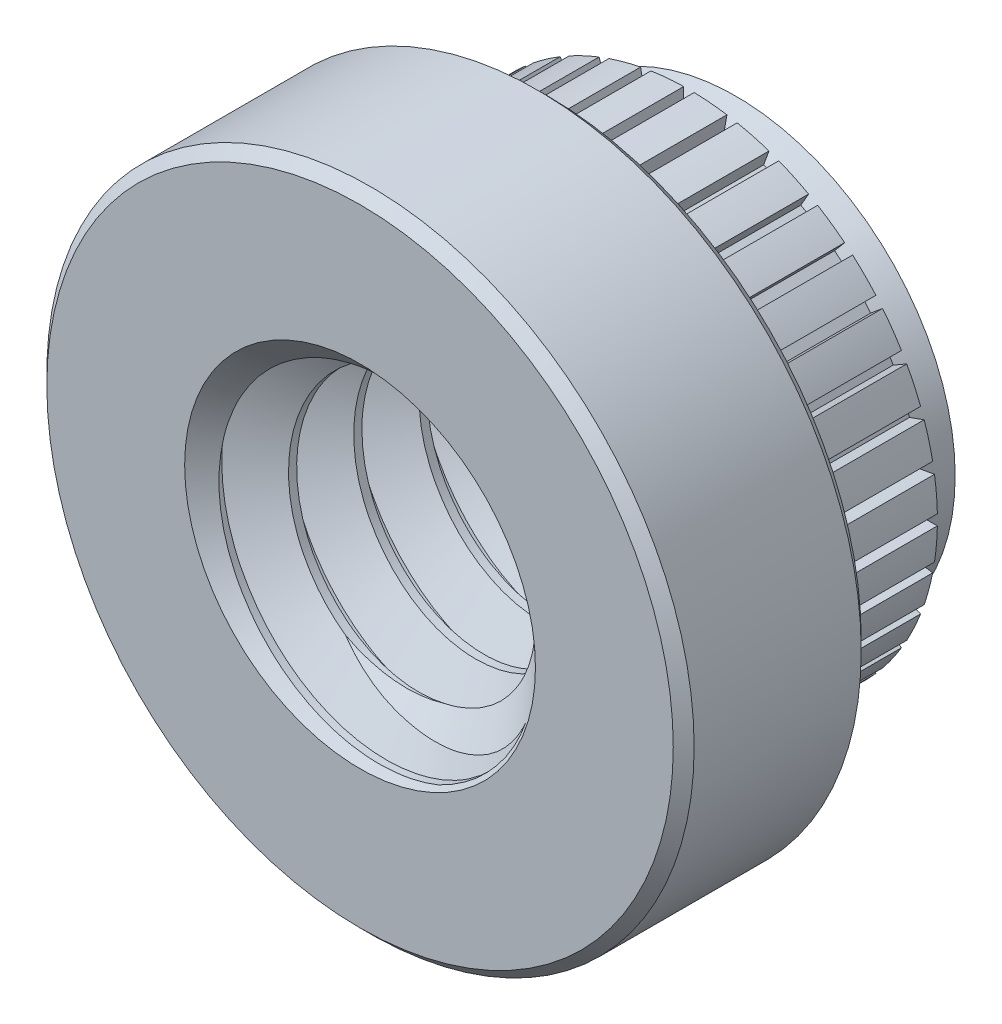
SolidWorks part; units mm, degrees
ref_plane "Front Plane" through (0, 0, 0) normal (0, 0, 1) x (1, 0, 0)
ref_plane "Top Plane" through (0, 0, 0) normal (0, 1, 0) x (1, 0, 0)
ref_plane "Right Plane" through (0, 0, 0) normal (1, 0, 0) x (0, 0, -1)
sketch "Sketch1" plane through (0, 0, 0) normal (0, 0, 1) x (1, 0, 0)
  circle A0 centre (0, 0) radius 3.937
  dimension "A" = 7.874
extrude "Extrude1" add sketch "Sketch1" against normal blind 2.286
sketch "Sketch15" plane through (0, 0, -2.286) normal (0, 0, -1) x (-1, 0, 0)
  circle A0 centre (0, 0) radius 2.7051
  dimension "hole dia" = 5.4102
sketch "Sketch2" plane through (0, 0, -2.286) normal (0, 0, -1) x (-1, 0, 0)
  circle A0 centre (0, 0) radius 3.0226
  dimension "D1" = 6.0452
extrude "Extrude2" add sketch "Sketch2" along normal blind 2.286
sketch "Sketch3" plane through (0, 0, -4.572) normal (0, 0, -1) x (-1, 0, 0)
  line L0 (0, 2.8321) -> (0, 3.937)
  circle A1 centre (0, 0) radius 3.937 construction
  circle A2 centre (0, 0) radius 2.8321
  circle A3 centre (0, 0) radius 2.8321 construction
  dimension "D1" = 0.1905
extrude "Cut-Extrude-Thin1" cut sketch "Sketch3" against normal up to surface (2.286 mm away) thin up to face at (3.937, 0, -2.286) thin type mid plane wall 0.127
pattern_circular "CirPattern1" count 36 over 360 about axis through (0, 0, 0) along (0, 0, 1) of "Cut-Extrude-Thin1"
sketch "Sketch5" plane through (0, 0, -4.572) normal (0, 0, -1) x (-1, 0, 0)
  circle A0 centre (0, 0) radius 3.937 construction
  circle A3 centre (0, 0) radius 2.667
  dimension "C" = 5.334
extrude "Cut-Extrude1" cut sketch "Sketch5" against normal blind 0.5715 draft 20 flip side to cut draft outward yes
chamfer "Chamfer2" distance 0.127 angle 45 2 edges at (3.937, 0, 0) (3.937, 0, -2.286)
sketch "Sketch7" plane through (0, 0, 0) normal (0, 0, 1) x (1, 0, 0)
  circle A0 centre (0, 0) radius 2.0828
  dimension "Thread Od" = 4.1656
extrude "Cut-Extrude3" cut sketch "Sketch7" against normal through all
sketch "Sketch8" plane through (0, 0, -4.572) normal (0, 0, -1) x (-1, 0, 0)
  circle A0 centre (0, 0) radius 2.0828 construction
  circle A1 centre (0, 0) radius 2.0828
curve "Helix/Spiral1" pitch 0.7937 height 7.747 turns 9.76 parameters "pitch"=0.7937
sketch "Sketch9" plane through (0, 0, 0) normal (1, 0, 0) x (0, 0, -1)
  line L0 (5.2665, 2.0828) -> (4.9689, 1.5672)
  line L1 (4.9689, 1.5672) -> (4.8697, 1.5672)
  line L2 (4.8697, 1.5672) -> (4.572, 2.0828)
  line L3 (5.2665, 2.0828) -> (4.572, 2.0828)
  line L4 (4.9193, 2.0828) -> (4.9193, 1.5672) construction
  line L5 (5.1177, 1.825) -> (4.7208, 1.825) construction
  line L6 (4.572, -2.0828) -> (4.572, 2.0828) construction
  dimension "D1" = 60
  dimension "D2" = 0.0992
  dimension "D3" = 0.3969
sweep "Sweep1" add profiles "Sketch9" path "Helix/Spiral1"
sketch "Sketch10" plane through (0, 0, 0) normal (0, 0, 1) x (1, 0, 0)
  circle A0 centre (0, 0) radius 3.937 construction
  circle A1 centre (0, 0) radius 3.937
extrude "Cut-Extrude4" cut sketch "Sketch10" along normal through all
sketch "Sketch11" plane through (0, 0, -4.572) normal (0, 0, -1) x (-1, 0, 0)
  circle A1 centre (0, 0) radius 2.667 construction
  circle A2 centre (0, 0) radius 2.667
extrude "Cut-Extrude5" cut sketch "Sketch11" along normal through all
sketch "Sketch13" plane through (0, 0, 0) normal (0, 0, 1) x (1, 0, 0)
  circle A2 centre (0, 0) radius 2.1336
  circle A3 centre (0, 0) radius 2.1336
  dimension "D1" = 0.0508
extrude "Cut-Extrude6" cut sketch "Sketch13" against normal through all draft 45
sketch "Sketch14" plane through (0, 0, -4.572) normal (0, 0, -1) x (-1, 0, 0)
  circle A2 centre (0, 0) radius 2.1336
  circle A3 centre (0, 0) radius 2.1336
  dimension "D1" = 0.0508
extrude "Cut-Extrude7" cut sketch "Sketch14" against normal through all draft 45
equation "\"D3@Helix/Spiral1\" = \"B@Extrude1\"+\"panel min.@Extrude2\"+.125"
equation "\"D2@Sketch9\" = \"pitch@Helix/Spiral1\"*.125"
equation "\"D3@Sketch9\" = \"pitch@Helix/Spiral1\"*.50"
equation "\"D1@Sketch2\" = \"hole dia@Sketch15\"+.025"
equation "\"D1@Cut-Extrude1\" = \"panel min.@Extrude2\"*.25"
